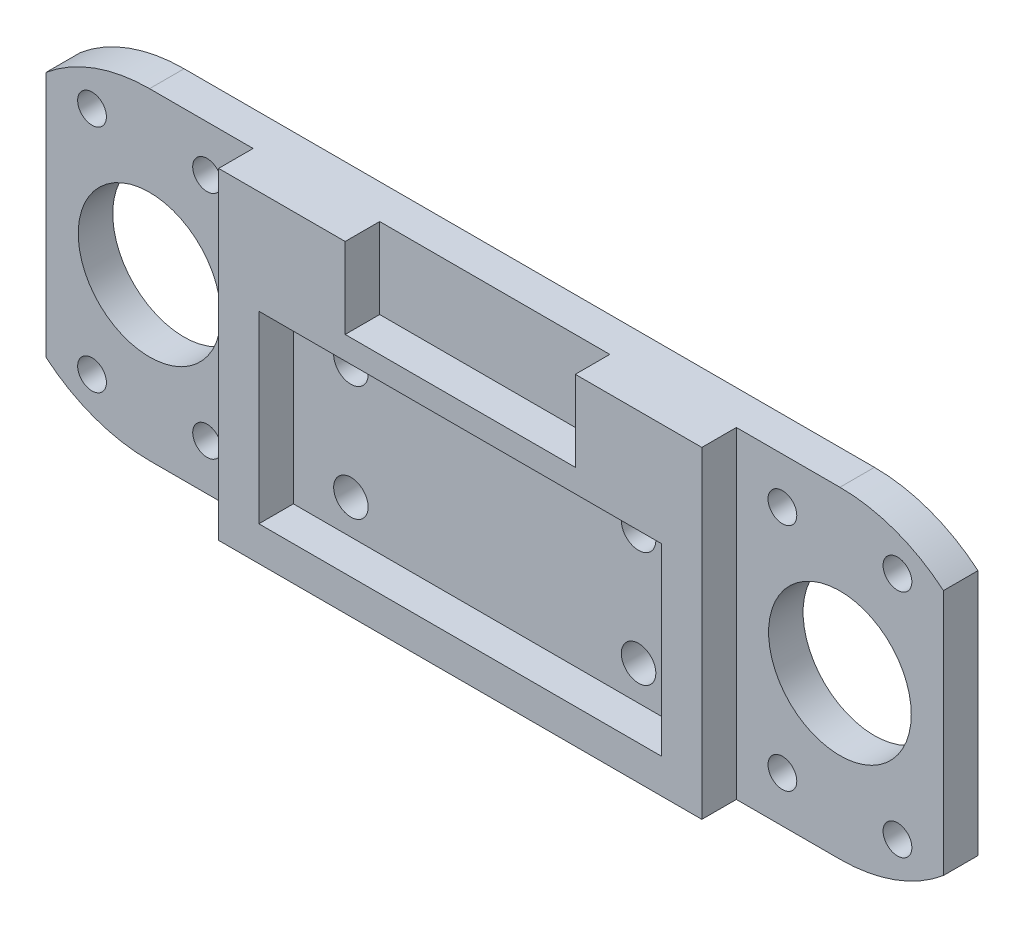
SolidWorks part; units mm, degrees
ref_plane "Front Plane" through (0, 0, 0) normal (0, 0, 1) x (1, 0, 0)
ref_plane "Top Plane" through (0, 0, 0) normal (0, 1, 0) x (1, 0, 0)
ref_plane "Right Plane" through (0, 0, 0) normal (1, 0, 0) x (0, 0, -1)
sketch "Sketch1" plane through (0, 0, 0) normal (0, 0, 1) x (1, 0, 0)
  line L0 (-39, 10.7238) -> (-39, -10.7238)
  line L1 (-30, -14) -> (30, -14)
  line L3 (-35, 10) -> (-25, -10) construction
  line L4 (-35, -10) -> (-25, 10) construction
  line L5 (-30, 14) -> (30, 14)
  line L6 (-30, 0) -> (30, 0) construction
  line L7 (39, 10.7238) -> (39, -10.7238)
  line L8 (25, 10) -> (35, -10) construction
  line L9 (35, 10) -> (25, -10) construction
  arc A0 (-30, 14) -> (-39, 10.7238) centre (-30, 0) ccw
  arc A1 (-39, -10.7238) -> (-30, -14) centre (-30, 0) ccw
  circle A2 centre (-30, 0) radius 6.2
  circle A3 centre (-35, 10) radius 1.25
  circle A4 centre (-25, 10) radius 1.25
  circle A5 centre (-35, -10) radius 1.25
  circle A6 centre (-25, -10) radius 1.25
  arc A7 (30, -14) -> (39, -10.7238) centre (30, 0) ccw
  arc A8 (39, 10.7238) -> (30, 14) centre (30, 0) ccw
  circle A9 centre (30, 0) radius 6.2
  circle A10 centre (25, 10) radius 1.25
  circle A11 centre (35, 10) radius 1.25
  circle A12 centre (25, -10) radius 1.25
  circle A13 centre (35, -10) radius 1.25
  point P7 (0, 0)
  point P8 (0, 0)
  point P9 (0, 0)
  point P18 (-30, 0)
  point P25 (30, 0)
  point P36 (30, 0)
  dimension "D2" = 14
  dimension "D3" = 12.4
  dimension "D6" = 2.5
  dimension "D8" = 2.5
  dimension "D4" = 20
  dimension "D5" = 10
  dimension "D7" = 60
  dimension "D9" = 10
  dimension "D10" = 20
  dimension "D16" = 9
extrude "Main" add sketch "Sketch1" along normal mid plane 3
sketch "Sketch2" plane through (0, 0, 1.5) normal (0, 0, -1) x (-1, 0, 0)
  line L0 (30, -14) -> (-30, -14) construction
  line L1 (39, 10.7238) -> (39, -10.7238) construction
  line L2 (21, 14) -> (10, 14)
  line L3 (21, 14) -> (21, -14)
  line L4 (21, -14) -> (-21, -14)
  line L5 (-21, 14) -> (-21, -14)
  line L6 (17.5, 5) -> (-17.5, 5)
  line L7 (17.5, 5) -> (17.5, -11)
  line L8 (17.5, -11) -> (-17.5, -11)
  line L9 (-17.5, 5) -> (-17.5, -11)
  line L10 (-39, -10.7238) -> (-39, 10.7238) construction
  line L11 (-30, 14) -> (30, 14) construction
  line L12 (-39, -10.7238) -> (-39, 10.7238) construction
  line L13 (-30, 14) -> (30, 14) construction
  line L14 (10, 14) -> (10, 7)
  line L15 (10, 7) -> (-10, 7)
  line L16 (-10, 7) -> (-10, 14)
  line L17 (-10, 14) -> (-21, 14)
  point P14 (0, 7)
  point P22 (0, 5)
  point P27 (17.5, -3)
  dimension "D1" = 16
  dimension "D2" = 3.5
  dimension "D3" = 18
  dimension "D4" = 7
  dimension "D5" = 35
  dimension "D6" = 78
  dimension "D7" = 18
  dimension "D8" = 3.5
  dimension "D9" = 3
  dimension "D10" = 2
  dimension "D11" = 20
  dimension "D12" = 3
extrude "Framework" add sketch "Sketch2" against normal blind 3
sketch "Sketch3" plane through (0, 0, -1.5) normal (0, 0, -1) x (-1, 0, 0)
  line L6 (17.5, 5) -> (17.5, -11) construction
  line L9 (17.5, -11) -> (-17.5, -11) construction
  circle A1 centre (12.5, -8) radius 1.5
  point P0 (17.5, -3)
  point P8 (16.2251, -12)
  dimension "D1" = 3
  dimension "D2" = 5
  dimension "D3" = 12.5
  dimension "D4" = 8
  dimension "D5" = 5
  dimension "D6" = 3
extrude "FixHole" cut sketch "Sketch3" against normal through all
pattern_linear "HolePattern" count 2 spacing 25 along (1, 0, 0) count 2 spacing 10 along (0, 1, 0) of "FixHole"
